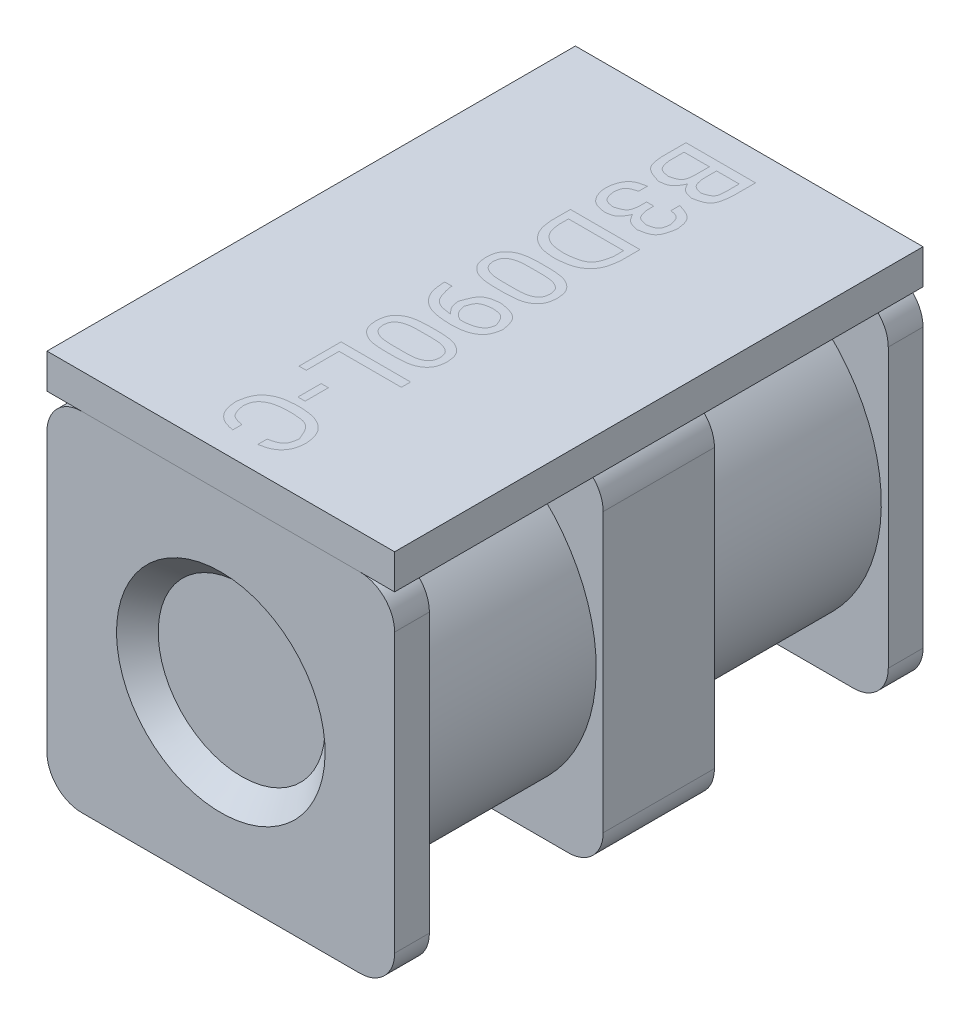
SolidWorks part; units mm, degrees
ref_plane "Спереди" through (0, 0, 0) normal (0, 0, 1) x (1, 0, 0)
ref_plane "Сверху" through (0, 0, 0) normal (0, 1, 0) x (1, 0, 0)
ref_plane "Справа" through (0, 0, 0) normal (1, 0, 0) x (0, 0, -1)
sketch "Эскиз1" plane through (0, 0, 0) normal (1, 0, 0) x (0, 0, -1)
  line L1 (-0.8, 5) -> (0.8, 5)
  line L2 (-0.8, 5) -> (-0.8, 0)
  line L3 (-0.8, 0) -> (0.8, 0)
  line L4 (0.8, 5) -> (0.8, 0)
  line L5 (-3.8, 5) -> (-3.3, 5)
  line L6 (-3.8, 5) -> (-3.8, 0)
  line L7 (-3.8, 0) -> (-3.3, 0)
  line L8 (-3.3, 5) -> (-3.3, 0)
  line L9 (3.3, 5) -> (3.8, 5)
  line L10 (3.3, 5) -> (3.3, 0)
  line L11 (3.3, 0) -> (3.8, 0)
  line L12 (3.8, 5) -> (3.8, 0)
  dimension "D1" = 5
  dimension "D2" = 1.6
  dimension "D3" = 0.5
  dimension "D4" = 7.6
  dimension "D5" = 3.8
  dimension "D6" = 0.8
extrude "Бобышка-Вытянуть1" add sketch "Эскиз1" along normal mid plane 5
fillet "Скругление1" radius 0.5 4 edges at (-2.5, 5, 3.55) (-2.5, 0, 3.55) (2.5, 0, 3.55) (2.5, 5, 3.55)
fillet "Скругление2" radius 0.5 4 edges at (2.5, 5, 0) (2.5, 0, 0) (-2.5, 0, 0) (-2.5, 5, 0)
fillet "Скругление3" radius 0.5 4 edges at (-2.5, 5, -3.55) (-2.5, 0, -3.55) (2.5, 0, -3.55) (2.5, 5, -3.55)
sketch "Эскиз2" plane through (0, 0, 0) normal (0, 0, 1) x (1, 0, 0)
  circle A0 centre (0, 2.5) radius 2.4
  point P2 (1.1071, 2.4356)
  point P4 (0, 0)
  dimension "D1" = 4.8
  dimension "D2" = 2.5
extrude "Бобышка-Вытянуть2" add sketch "Эскиз2" along normal up to surface (3.3 mm away) and the other way up to surface (3.3 mm away) up to face at (0, 2.5, 3.3) other way up to face at (0, 2.5, -3.3)
sketch "Эскиз3" plane through (0, 5, 0) normal (0, 1, 0) x (1, 0, 0)
  line L0 (2, 3.8) -> (-2, 3.8) construction
  line L1 (2.5, 3.8) -> (-2.5, 3.8)
  line L2 (2.5, 3.8) -> (2.5, -3.8)
  line L3 (2.5, -3.8) -> (-2.5, -3.8)
  line L4 (-2.5, 3.8) -> (-2.5, -3.8)
  line L5 (2, -3.8) -> (-2, -3.8) construction
  line L6 (-2.5, 3.3) -> (-2.5, 3.8) construction
  line L7 (2.5, 3.8) -> (2.5, 3.3) construction
extrude "Бобышка-Вытянуть3" add sketch "Эскиз3" along normal blind 0.5 separate body
sketch "Эскиз4" plane through (0, 5.5, 0) normal (0, 1, 0) x (1, 0, 0)
  line L0 (-0.5, 3.8) -> (-0.5, -3.8) construction
  line L1 (2.5, 3.8) -> (-2.5, 3.8) construction
  line L2 (-2.5, -3.8) -> (2.5, -3.8) construction
  line L3 (-2.5, 3.8) -> (-2.5, -3.8) construction
  text T0 "B3D090L-C" font "Roboto" height 1
  point P3 (0, 0)
  point P6 (0, 0)
  dimension "D1" = 2
wrap "Перенос1" sketch "Эскиз4" wrap type scribe source sketch "Эскиз4" face at (0, 5.5, 0)
sketch "Эскиз6" plane through (0, 0, -3.8) normal (0, 0, -1) x (-1, 0, 0)
  line L0 (-2, 0) -> (2, 0) construction
  circle A0 centre (0, 2.5) radius 1.5
  point P4 (0, 0)
  point P5 (0, 0)
  point P6 (0, 0)
  dimension "D1" = 3
  dimension "D2" = 2.5
extrude "Вырез-Вытянуть1" cut sketch "Эскиз6" against normal blind 0.3 draft 45
mirror "Зеркальное отражение1" about plane through (0, 0, 0) normal (0, 0, 1) of "Вырез-Вытянуть1"
equation "\"D5@Эскиз1\"=\"D4@Эскиз1\"/2"
equation "\"D6@Эскиз1\"=\"D2@Эскиз1\"/2"
